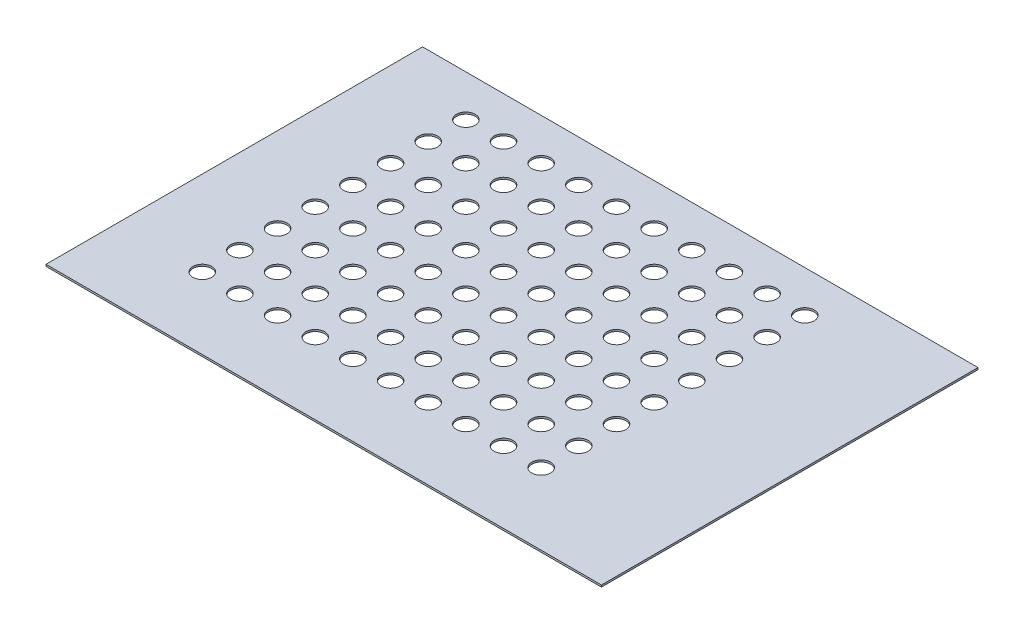
SolidWorks part; units mm, degrees
ref_plane "Front Plane" through (0, 0, 0) normal (0, 0, 1) x (1, 0, 0)
ref_plane "Top Plane" through (0, 0, 0) normal (0, 1, 0) x (1, 0, 0)
ref_plane "Right Plane" through (0, 0, 0) normal (1, 0, 0) x (0, 0, -1)
sketch "Sketch1" plane through (0, 0, 0) normal (0, 1, 0) x (1, 0, 0)
  line L1 (-108.5034, 75.9524) -> (186.4966, 75.9524)
  line L2 (-108.5034, 75.9524) -> (-108.5034, -124.0476)
  line L3 (-108.5034, -124.0476) -> (186.4966, -124.0476)
  line L4 (186.4966, 75.9524) -> (186.4966, -124.0476)
  dimension "D1" = 295
  dimension "D2" = 200
base flange "Base-Flange1" sketch "Sketch1" thickness 1 reverse thickness direction no parameters "D1"=0.7366
sketch "Sketch2" plane through (0, 0, 0) normal (0, 1, 0) x (1, 0, 0)
  line L0 (-108.5034, 75.9524) -> (-108.5034, -124.0476) construction
  circle A0 centre (-63.5034, 53.9521) radius 5
  circle A1 centre (-63.5034, 33.9521) radius 5
  circle A2 centre (-63.5034, 13.9521) radius 5
  circle A3 centre (-63.5034, -6.0479) radius 5
  circle A4 centre (-63.5034, -26.0479) radius 5
  circle A5 centre (-63.5034, -46.0479) radius 5
  circle A48 centre (-63.5034, -66.0479) radius 5
  circle A49 centre (-63.5034, -86.0479) radius 5
  circle A64 centre (-43.5034, 53.9521) radius 5
  circle A65 centre (-43.5034, 33.9521) radius 5
  circle A66 centre (-43.5034, 13.9521) radius 5
  circle A67 centre (-43.5034, -6.0479) radius 5
  circle A68 centre (-43.5034, -26.0479) radius 5
  circle A69 centre (-43.5034, -46.0479) radius 5
  circle A70 centre (-43.5034, -66.0479) radius 5
  circle A71 centre (-43.5034, -86.0479) radius 5
  circle A72 centre (-23.5034, 53.9521) radius 5
  circle A73 centre (-23.5034, 33.9521) radius 5
  circle A74 centre (-23.5034, 13.9521) radius 5
  circle A75 centre (-23.5034, -6.0479) radius 5
  circle A76 centre (-23.5034, -26.0479) radius 5
  circle A77 centre (-23.5034, -46.0479) radius 5
  circle A78 centre (-23.5034, -66.0479) radius 5
  circle A79 centre (-23.5034, -86.0479) radius 5
  circle A80 centre (-3.5034, 53.9521) radius 5
  circle A81 centre (-3.5034, 33.9521) radius 5
  circle A82 centre (-3.5034, 13.9521) radius 5
  circle A83 centre (-3.5034, -6.0479) radius 5
  circle A84 centre (-3.5034, -26.0479) radius 5
  circle A85 centre (-3.5034, -46.0479) radius 5
  circle A86 centre (-3.5034, -66.0479) radius 5
  circle A87 centre (-3.5034, -86.0479) radius 5
  circle A88 centre (16.4966, 53.9521) radius 5
  circle A89 centre (16.4966, 33.9521) radius 5
  circle A90 centre (16.4966, 13.9521) radius 5
  circle A91 centre (16.4966, -6.0479) radius 5
  circle A92 centre (16.4966, -26.0479) radius 5
  circle A93 centre (16.4966, -46.0479) radius 5
  circle A94 centre (16.4966, -66.0479) radius 5
  circle A95 centre (16.4966, -86.0479) radius 5
  circle A96 centre (36.4966, 53.9521) radius 5
  circle A97 centre (36.4966, 33.9521) radius 5
  circle A98 centre (36.4966, 13.9521) radius 5
  circle A99 centre (36.4966, -6.0479) radius 5
  circle A100 centre (36.4966, -26.0479) radius 5
  circle A101 centre (36.4966, -46.0479) radius 5
  circle A102 centre (36.4966, -66.0479) radius 5
  circle A103 centre (36.4966, -86.0479) radius 5
  circle A104 centre (56.4966, 53.9521) radius 5
  circle A105 centre (56.4966, 33.9521) radius 5
  circle A106 centre (56.4966, 13.9521) radius 5
  circle A107 centre (56.4966, -6.0479) radius 5
  circle A108 centre (56.4966, -26.0479) radius 5
  circle A109 centre (56.4966, -46.0479) radius 5
  circle A110 centre (56.4966, -66.0479) radius 5
  circle A111 centre (56.4966, -86.0479) radius 5
  circle A112 centre (76.4966, 53.9521) radius 5
  circle A113 centre (76.4966, 33.9521) radius 5
  circle A114 centre (76.4966, 13.9521) radius 5
  circle A115 centre (76.4966, -6.0479) radius 5
  circle A116 centre (76.4966, -26.0479) radius 5
  circle A117 centre (76.4966, -46.0479) radius 5
  circle A118 centre (76.4966, -66.0479) radius 5
  circle A119 centre (76.4966, -86.0479) radius 5
  circle A120 centre (96.4966, 53.9521) radius 5
  circle A121 centre (96.4966, 33.9521) radius 5
  circle A122 centre (96.4966, 13.9521) radius 5
  circle A123 centre (96.4966, -6.0479) radius 5
  circle A124 centre (96.4966, -26.0479) radius 5
  circle A125 centre (96.4966, -46.0479) radius 5
  circle A126 centre (96.4966, -66.0479) radius 5
  circle A127 centre (96.4966, -86.0479) radius 5
  circle A128 centre (116.4966, 53.9521) radius 5
  circle A129 centre (116.4966, 33.9521) radius 5
  circle A130 centre (116.4966, 13.9521) radius 5
  circle A131 centre (116.4966, -6.0479) radius 5
  circle A132 centre (116.4966, -26.0479) radius 5
  circle A133 centre (116.4966, -46.0479) radius 5
  circle A134 centre (116.4966, -66.0479) radius 5
  circle A135 centre (116.4966, -86.0479) radius 5
  dimension "D1" = 10
  dimension "D5" = 20
  dimension "D6" = 45
  dimension "D2" = 8
extrude "Cut-Extrude1" cut sketch "Sketch2" against normal through all normal cut yes
sketch "Bend-Lines1" [suppressed] plane through (0, 0, 0) normal (0, 1, 0) x (1, 0, 0)
sketch "Bounding-Box1" [suppressed] plane through (0, 0, 0) normal (0, 1, 0) x (1, 0, 0)
sheet metal parameters "Sheet-Metal1" thickness 1 parameters "D1"=0.7366
flat pattern "Flat-Pattern1" [suppressed]
sketch "Bend-Lines2" plane through (0, 0, 0) normal (0, 1, 0) x (1, 0, 0)
sketch3d "Bounding-Box2" [suppressed]
  line L0 (176.4966, -124.0476, 0) -> (-108.5034, -124.0476, 0) construction
  line L1 (176.4966, 75.9524, 0) -> (-108.5034, 75.9524, 0) construction
  line L2 (176.4966, -124.0476, 0) -> (176.4966, 75.9524, 0) construction
  line L3 (-108.5034, -124.0476, 0) -> (-108.5034, 75.9524, 0) construction
sheet metal parameters "Sheet-Metal2" thickness 1 parameters "D1"=0.7366
flat pattern "Flat-Pattern1"
sketch "Bend-Lines2" plane through (0, 0, 0) normal (0, 1, 0) x (1, 0, 0)
sketch3d "Bounding-Box2" [suppressed]
  line L0 (186.4966, -124.0476, 0) -> (-108.5034, -124.0476, 0) construction
  line L1 (186.4966, 75.9524, 0) -> (-108.5034, 75.9524, 0) construction
  line L2 (186.4966, -124.0476, 0) -> (186.4966, 75.9524, 0) construction
  line L3 (-108.5034, -124.0476, 0) -> (-108.5034, 75.9524, 0) construction
